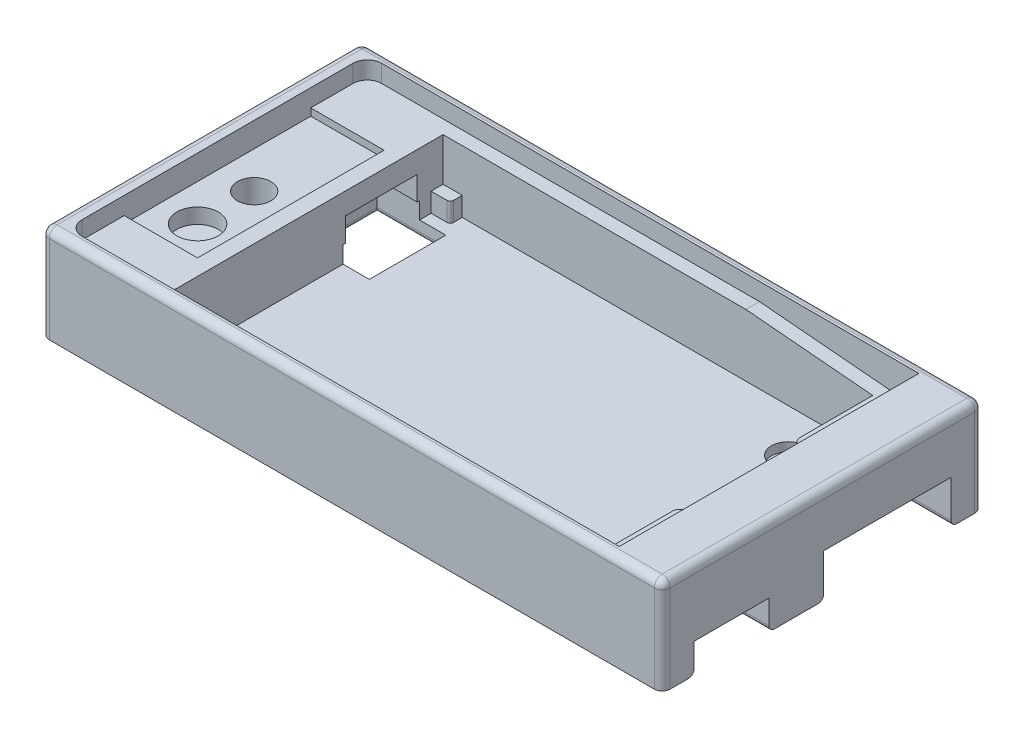
SolidWorks part; units mm, degrees
ref_plane "前视基准面" through (0, 0, 0) normal (0, 0, 1) x (1, 0, 0)
ref_plane "上视基准面" through (0, 0, 0) normal (0, 1, 0) x (1, 0, 0)
ref_plane "右视基准面" through (0, 0, 0) normal (1, 0, 0) x (0, 0, -1)
other "Configuration Table"
sketch "草图1" plane through (0, 0, 0) normal (0, 1, 0) x (1, 0, 0)
  line L0 (-38.945, 0) -> (38.945, 0) construction
  line L1 (-38.945, 20.1) -> (38.945, 20.1)
  line L2 (-38.945, 20.1) -> (-38.945, -20.1)
  line L3 (-38.945, -20.1) -> (38.945, -20.1)
  line L4 (38.945, 20.1) -> (38.945, -20.1)
  line L5 (-38.945, 20.1) -> (38.945, -20.1) construction
  line L6 (-38.945, -20.1) -> (38.945, 20.1) construction
  line L7 (-25.745, -17.1) -> (28.155, -17.1)
  line L8 (-25.745, -17.1) -> (-25.745, 17.1)
  line L9 (-25.745, 17.1) -> (28.155, 17.1)
  line L10 (28.155, -17.1) -> (28.155, 17.1)
  line L12 (32.245, 6.9973) -> (34.445, 6.9973)
  line L13 (32.245, 6.9973) -> (32.245, -6.9973)
  line L14 (32.245, -6.9973) -> (34.445, -6.9973)
  line L15 (34.445, 6.9973) -> (34.445, -6.9973)
  line L16 (-36.945, 18.8) -> (32.245, 18.8)
  line L17 (-36.945, 18.8) -> (-36.945, -18.8)
  line L18 (-36.945, -18.8) -> (32.245, -18.8)
  line L19 (32.245, 18.8) -> (32.245, -18.8)
  circle A0 centre (-32.345, 7.1) radius 2.6
  circle A1 centre (-32.345, 0) radius 2.1
  circle A2 centre (22.955, 11.6973) radius 2.1
  circle A3 centre (22.955, -11.6973) radius 2.1
  circle A4 centre (-32.345, -7.1) radius 2.6
  point P0 (0, 0)
  dimension "D1" = 4.2
  dimension "D6" = 5.2
  dimension "D2" = 5.2
  dimension "D3" = 5.4027
  dimension "D4" = 6.6
  dimension "D5" = 13
  dimension "D7" = 3
  dimension "D8" = 3
  dimension "D9" = 6.6
  dimension "D10" = 10.79
  dimension "D11" = 53.9
  dimension "D12" = 34.2
  dimension "D13" = 2.2
  dimension "D14" = 4.7
  dimension "D15" = 1.3
  dimension "D16" = 1.3
  dimension "D17" = 2
  dimension "D18" = 6.7
extrude "凸台-拉伸2" add sketch "草图1" along normal blind 2.2 contours L4 L1 L2 L3 L16 L19 L10 L12 L15 L14 L18 L17 | L15 L12 L10 L14 region at (0, 0, -19.2235) region at (33.345, 0, 0)
extrude "凸台-拉伸3" add sketch "草图1<4>" against normal blind 7.8 contours L19 L16 L17 L18 L7 L8 L9 A0 A1 A4 | L4 L1 L2 L3 L16 L19 L10 L12 L15 L14 L18 L17 | A4 | A0 | A1 | L15 L12 L13 L14 region at (0, 0, -19.2235) region at (33.345, 0, 0) region at (31.4575, 0, 0) region at (-32.345, 0, -7.1) region at (-32.345, 0, 0) region at (-32.345, 0, 7.1)
sketch "草图1<4>" plane through (0, 0, 0) normal (0, 1, 0) x (1, 0, 0) same geometry as "草图1"
sketch "草图2" plane through (0, 0, 0) normal (0, 1, 0) x (1, 0, 0)
  line L0 (-36.945, 18.8) -> (-36.945, -18.8) construction
  line L1 (-36.945, 11.7) -> (-27.745, 11.7)
  line L2 (-36.945, 11.7) -> (-36.945, -11.7)
  line L3 (-36.945, -11.7) -> (-27.745, -11.7)
  line L4 (-27.745, 11.7) -> (-27.745, -11.7)
  circle A0 centre (-32.345, 7.1) radius 2.6 construction
  circle A1 centre (-32.345, 7.1) radius 2.6 construction
  circle A2 centre (-32.345, -7.1) radius 2.6 construction
  circle A3 centre (-32.345, -7.1) radius 2.6 construction
  dimension "D1" = 4.6
  dimension "D2" = 4.6
  dimension "D3" = 4.6
extrude "切除-拉伸1" cut sketch "草图2" against normal blind 0.9
sketch "草图6" plane through (0, -0.9, 0) normal (0, 1, 0) x (1, 0, 0)
  circle A0 centre (-32.345, 7.1) radius 2.6 construction
  circle A1 centre (-32.345, 7.1) radius 2.6
  circle A2 centre (-32.345, -7.1) radius 2.6 construction
  circle A3 centre (-32.345, -7.1) radius 2.6
extrude "切除-拉伸2" cut sketch "草图6" against normal blind 1.9 contours A3 region at (-32.345, -0.9, 7.1)
sketch "草图7" plane through (0, -0.9, 0) normal (0, 1, 0) x (1, 0, 0)
  circle A0 centre (-32.345, 0) radius 2.1 construction
  circle A1 centre (-32.345, 0) radius 2.1
extrude "切除-拉伸3" cut sketch "草图7" against normal blind 1.1
sketch "草图8" plane through (0, -2, 0) normal (0, 1, 0) x (1, 0, 0)
  circle A0 centre (-32.345, 0) radius 1.2
  dimension "2.2" = 2.4
extrude "切除-拉伸4" cut sketch "草图8" against normal through all
sketch "草图9" plane through (0, -7.8, 0) normal (0, -1, 0) x (1, 0, 0)
  line L0 (38.945, -20.1) -> (38.945, 20.1) construction
  line L1 (-38.945, -20.1) -> (38.945, -20.1) construction
  line L2 (-38.945, -20.1) -> (-38.945, 20.1) construction
  line L3 (-38.945, 20.1) -> (38.945, 20.1) construction
  line L4 (38.945, -20.1) -> (38.945, 20.1)
  line L5 (-38.945, -20.1) -> (38.945, -20.1)
  line L6 (-38.945, -20.1) -> (-38.945, 20.1)
  line L7 (-38.945, 20.1) -> (38.945, 20.1)
extrude "凸台-拉伸4" add sketch "草图9" along normal blind 2
sketch "草图10" plane through (0, -7.8, 0) normal (0, 1, 0) x (1, 0, 0)
  circle A0 centre (22.955, -11.6973) radius 2.1 construction
  circle A1 centre (22.955, 11.6973) radius 2.1 construction
  circle A2 centre (22.955, -11.6973) radius 2.1
  circle A3 centre (22.955, 11.6973) radius 2.1
extrude "切除-拉伸5" cut sketch "草图10" against normal blind 1.1
sketch "草图11" plane through (0, -8.9, 0) normal (0, 1, 0) x (1, 0, 0)
  circle A0 centre (22.955, 11.6973) radius 1.2
  circle A1 centre (22.955, -11.6973) radius 1.2
  dimension "D1" = 2.4
  dimension "D2" = 2.4
extrude "切除-拉伸6" cut sketch "草图11" against normal through all
sketch "草图12" plane through (0, -9.8, 0) normal (0, -1, 0) x (1, 0, 0)
  line L0 (-25.745, -17.1) -> (28.155, -17.1) construction
  line L1 (-25.745, -17.1) -> (28.155, -17.1) construction
  line L7 (-30.5189, -4.85) -> (-26.0689, -4.85)
  line L8 (-30.5189, -4.85) -> (-30.5189, -13.85)
  line L9 (-30.5189, -13.85) -> (-26.0689, -13.85)
  line L10 (-26.0689, -4.85) -> (-26.0689, -13.85)
  line L11 (-30.5189, -4.85) -> (-26.0689, -13.85) construction
  line L12 (-30.5189, -13.85) -> (-26.0689, -4.85) construction
  line L13 (-28.2939, -9.35) -> (-23.0895, -9.35) construction
  line L14 (-31.0689, -4.55) -> (-26.0689, -4.55)
  line L15 (-31.0689, -4.55) -> (-31.0689, -14.15)
  line L16 (-31.0689, -14.15) -> (-26.0689, -14.15)
  line L17 (-26.0689, -4.55) -> (-26.0689, -14.15)
  point P6 (-28.2939, -9.35)
  dimension "D1" = 7.75
  dimension "D2" = 4.45
  dimension "D3" = 9
  dimension "D4" = 9.6
  dimension "D5" = 5
extrude "切除-拉伸7" cut sketch "草图12" against normal blind 7.1 contours L10 L7 L8 L9 region at (-28.2939, -9.8, -9.35)
extrude "切除-拉伸8" cut sketch "草图12<3>" against normal offset from surface (4.1 mm away) 3 contours L17 L14 L15 L16 L9 L8 L7 region at (-30.6271, -9.8, -9.35) up to face at (-28.2939, -2.7, -9.35)
sketch "草图12<3>" plane through (0, -9.8, 0) normal (0, -1, 0) x (1, 0, 0) same geometry as "草图12"
sketch "草图13" plane through (-26.0689, 0, 0) normal (-1, 0, 0) x (0, 0, 1)
  line L4 (-4.85, -2.7) -> (-13.85, -2.7)
  line L5 (-4.85, -2.7) -> (-13.85, -2.7)
  line L9 (-13.85, -2.7) -> (-13.85, -5.7)
  line L11 (-13.85, -5.7) -> (-14.15, -5.7)
  line L12 (-14.15, -9.8) -> (-4.55, -9.8)
  line L13 (-13.85, -5.7) -> (-14.15, -5.7)
  line L14 (-14.15, -5.7) -> (-14.15, -9.8)
  line L15 (-4.85, -5.7) -> (-4.85, -2.7)
  line L17 (-13.85, -2.7) -> (-13.85, -5.7)
  line L20 (-14.15, -9.8) -> (-4.55, -9.8)
  line L23 (-4.85, -5.7) -> (-4.85, -2.7)
  line L24 (-14.15, -5.7) -> (-14.15, -9.8)
  line L25 (-4.55, -9.8) -> (-4.55, -5.7)
  line L26 (-4.55, -9.8) -> (-4.55, -5.7)
  line L27 (-4.55, -5.7) -> (-4.85, -5.7)
  line L28 (-4.55, -5.7) -> (-4.85, -5.7)
  dimension "D1" = 0
extrude "切除-拉伸9" cut sketch "草图13" against normal up to surface (0.3239 mm away) up to face at (-25.745, -3.9, 0)
sketch "草图14" plane through (-25.745, 0, 0) normal (-1, 0, 0) x (0, 0, 1)
  line L4 (-14.15, -7.8) -> (-14.15, -9.8)
  line L5 (-14.15, -9.8) -> (-4.55, -9.8)
  line L7 (-4.55, -7.8) -> (-14.15, -7.8)
  line L9 (-14.15, -9.8) -> (-4.55, -9.8)
  line L11 (-4.55, -7.8) -> (-14.15, -7.8)
  line L12 (-14.15, -7.8) -> (-14.15, -9.8)
  line L14 (-4.55, -9.8) -> (-4.55, -7.8)
  line L15 (-4.55, -9.8) -> (-4.55, -7.8)
  dimension "D1" = 0
extrude "切除-拉伸10" cut sketch "草图14" against normal blind 3.3
fillet "圆角1" radius 1.8 4 edges at (32.245, 1.1, 18.8) (32.245, 1.1, -18.8) (-36.945, 1.1, -18.8) (-36.945, 1.1, 18.8)
fillet "圆角2" radius 1 8 edges at (38.945, -3.8, -20.1) (38.945, 2.2, 0) (38.945, -3.8, 20.1) (0, 2.2, -20.1) (-38.945, -3.8, -20.1) (0, 2.2, 20.1) (-38.945, 2.2, 0) (-38.945, -3.8, 20.1)
sketch "草图15" plane through (0, -7.8, 0) normal (0, 1, 0) x (1, 0, 0)
  line L0 (0, 0) -> (25.0264, 0) construction
  line L1 (-25.745, 17.1) -> (-23.345, 17.1)
  line L2 (-25.745, 17.1) -> (-25.745, 15.6)
  line L3 (-25.745, 15.6) -> (-23.345, 15.6)
  line L4 (-23.345, 17.1) -> (-23.345, 15.6)
  line L5 (-25.745, -15.6) -> (-23.345, -15.6)
  line L6 (-23.345, -17.1) -> (-23.345, -15.6)
  line L7 (-25.745, -17.1) -> (-23.345, -17.1)
  line L8 (-25.745, -17.1) -> (-25.745, -15.6)
  dimension "D1" = 2.4
  dimension "D2" = 1.5
extrude "凸台-拉伸5" add sketch "草图15" along normal blind 2.4
sketch "草图16" plane through (0, 0, 0) normal (0, 1, 0) x (1, 0, 0)
  line L0 (0, 0) -> (31.9375, 0) construction
  line L1 (28.155, -17.1) -> (28.155, 17.1) construction
  line L3 (30.2966, 8) -> (30.2966, -8)
  line L4 (32.245, 17) -> (32.245, -17) construction
  line L6 (30.2966, 10.6491) -> (30.2966, 8)
  line L7 (30.2966, -10.6491) -> (30.2966, -8)
  arc A0 (29.9791, 7.2593) -> (30.2966, 10.6491) centre (31.5254, 8.8242) cw
  arc A1 (29.9791, -7.2593) -> (30.2966, -10.6491) centre (31.5254, -8.8242) ccw
  ellipse E0 centre (28.155, 0) end of major axis (28.155, -8.1106) minor radius 4.09 (29.9791, -7.2593) -> (29.9791, 7.2593) ccw
  dimension "D1" = 2.2
revolve "切除-旋转1" [suppressed] cut sketch "草图16" angle 360 about L3
sketch "草图17" plane through (0, -7.8, 0) normal (0, 1, 0) x (1, 0, 0)
  circle A1 centre (-32.345, 0) radius 1.2
  circle A2 centre (-32.345, 0) radius 1.2
  dimension "D1" = 0
extrude "切除-拉伸11" cut sketch "草图17" against normal through all
sketch "草图19" plane through (0, 0, 20.1) normal (0, 0, 1) x (1, 0, 0)
  line L0 (12.245, 0) -> (34.1356, 0.2) construction
  line L1 (32.245, 2.2) -> (30.445, 2.2) construction
  line L2 (12.245, 0) -> (32.245, 2) construction
  line L6 (12.245, 0) -> (12.245, 2)
  line L11 (12.245, 0) -> (34.045, -2) construction
  line L12 (12.245, 0) -> (32.2683, -1.7518)
  line L13 (12.245, 0) -> (33.7165, -4.2678) construction
  line L14 (32.245, 2) -> (32.245, 0) construction
  line L15 (32.245, 0) -> (30.245, 0) construction
  line L17 (12.245, 2) -> (12.245, 3)
  line L18 (12.245, 3) -> (32.245, 3)
  line L19 (32.245, 2) -> (32.245, 3)
  line L20 (32.245, 2.2) -> (30.445, 2.2) construction
  line L21 (-35.145, 0) -> (30.445, 0) construction
  line L22 (-35.145, 0) -> (30.245, 0) construction
  line L23 (12.245, 2) -> (32.245, 2) construction
  line L24 (34.1416, 0) -> (32.3448, 0) construction
  line L25 (30.245, 0) -> (34.045, 0) construction
  line L26 (30.245, 0) -> (30.245, -2) construction
  line L27 (30.245, -2) -> (34.045, -2) construction
  line L28 (34.045, 0) -> (34.045, -2) construction
  line L29 (33.7165, -4.2678) -> (25.7165, -2.6777)
  line L30 (25.7165, -2.6777) -> (25.8467, -1.19)
  line L31 (34.1356, 0.2) -> (32.3439, 0.1836)
  circle A0 centre (12.245, 0) radius 20.0998 construction
  arc A3 (32.245, 2) -> (32.2683, -1.7518) centre (12.245, 0) cw
  circle A4 centre (12.245, 0) radius 21.8916 construction
  arc A5 (33.7165, -4.2678) -> (34.1356, 0.2) centre (12.245, 0) ccw
  line M8 (37.945, 1.2) -> (-37.945, 1.2)
  dimension "D1" = 2
  dimension "D2" = 20
  dimension "D3" = 5
  dimension "D4" = 2
  dimension "D5" = 20
  dimension "D6" = 6
  dimension "D7" = 1
  dimension "D8" = 1.8
  dimension "D9" = 2
  dimension "D10" = 8
  dimension "D11" = 0.2
extrude "切除-拉伸12" cut sketch "草图19" against normal up to surface (38.9 mm away) from surface contours L6 L12 M8 | L6 M8 region at (23.6992, 0.0997, 20.1) region at (22.2527, 2.0995, 20.1) up to face at (-2.35, 1.1, -18.8) starting at face at (-2.35, 1.1, 18.8)
extrude "切除-拉伸13" cut sketch "草图19<3>" against normal up to vertex (27.0973 mm away) from vertex contours L27 L12 L13 region at (30.7271, -2.2329, 20.1) up to point (34.445, 0, -6.9973) starting at point (34.445, 0, 6.9973)
sketch "草图19<3>" plane through (0, 0, 20.1) normal (0, 0, 1) x (1, 0, 0) same geometry as "草图19"
sketch "草图20" plane through (0.3554, 2.3632, 0) normal (0.195, 0.9808, 0) x (0.9808, -0.195, 0)
  line L0 (0.1121, 0) -> (28.3434, 0) construction
  line L1 (28.3434, 6.9973) -> (28.3434, -6.9973) construction
  line L2 (28.3434, 6.9973) -> (28.3434, -6.9973) construction
  line L3 (28.3434, 5.3609) -> (28.3434, -5.3609)
  line L4 (28.3434, 0) -> (31.3095, 0) construction
  line L5 (31.3095, 18.8) -> (31.3095, -18.8) construction
  line L6 (29.3869, 4.2263) -> (28.3434, 5.3609) construction
  line L9 (28.3434, -5.3609) -> (28.3434, 5.3609) construction
  ellipse E0 centre (28.3434, 0) end of major axis (28.3434, 5.3609) minor radius 2.9661 (28.3434, 5.3609) -> (28.3434, -5.3609) cw
revolve "切除-旋转2" [suppressed] cut sketch "草图20" angle 360 about L3
fillet "圆角4" [suppressed] radius 1
fillet "圆角5" radius 0.4 2 edges at (-23.345, -6.6, 15.6) (-23.345, -6.6, -15.6)
sketch "草图21" plane through (0, -2, 0) normal (0, 1, 0) x (1, 0, 0)
  circle A1 centre (-32.345, 0) radius 2.1
  circle A2 centre (-32.345, 0) radius 2.1
  dimension "D1" = 0
extrude "切除-拉伸14" cut sketch "草图21" against normal up to surface (6.9 mm away) up to face at (22.955, -8.9, -10.4973)
sketch "草图22" plane through (0, -9.8, 0) normal (0, -1, 0) x (1, 0, 0)
  line L0 (0, 0) -> (39.25, 0) construction
  line L2 (-38.945, 14.6675) -> (-38.945, 5.2675)
  line L3 (31.045, 16.1208) -> (38.945, 16.1208)
  line L4 (31.045, 16.1208) -> (31.045, 6.7208)
  line L5 (31.045, 6.7208) -> (38.945, 6.7208)
  line L6 (38.945, 16.1208) -> (38.945, 6.7208)
  line L7 (31.045, 16.1208) -> (38.945, 6.7208) construction
  line L8 (31.045, 6.7208) -> (38.945, 16.1208) construction
  line L9 (-38.945, 14.6675) -> (-31.045, 14.6675)
  line L10 (-38.945, 5.2675) -> (-31.045, 5.2675)
  line L11 (-31.045, 14.6675) -> (-31.045, 5.2675)
  line L13 (38.945, -19.1) -> (38.945, 19.1) construction
  line L14 (-38.945, 19.1) -> (-38.945, -19.1) construction
  point P5 (34.995, 11.4208)
  dimension "D1" = 7.9
  dimension "D2" = 9.4
extrude "切除-拉伸15" cut sketch "草图22" against normal blind 3.7
sketch "草图23" plane through (0, -9.8, 0) normal (0, -1, 0) x (1, 0, 0)
  line L1 (38.945, -16.1357) -> (30.545, -16.1357)
  line L2 (38.945, -16.1357) -> (38.945, -0.1357)
  line L3 (38.945, -0.1357) -> (30.545, -0.1357)
  line L4 (30.545, -16.1357) -> (30.545, -0.1357)
  line L6 (32.2683, -18.8) -> (12.245, -18.8) construction
  line L7 (32.2683, -18.8) -> (12.245, -18.8) construction
  line L8 (38.945, -19.1) -> (38.945, 6.7208) construction
  line L9 (38.945, -19.1) -> (38.945, 6.7208) construction
  dimension "D1" = 8.4
  dimension "D2" = 16
extrude "切除-拉伸16" cut sketch "草图23" against normal blind 5.4
fillet "圆角6" radius 0.7 13 edges at (-34.995, -9.8, 5.2675) (34.745, -9.8, -16.1357) (30.545, -9.8, -8.1357) (34.745, -9.8, -0.1357) (34.995, -9.8, 6.7208) (34.995, -9.8, 16.1208) (31.045, -9.8, 11.4208) (-22.445, -9.8, -9.35) (-26.7569, -9.8, -14.15) (-31.0689, -9.8, -9.35) (-26.7569, -9.8, -4.55) (-31.045, -9.8, 9.9675) (-34.995, -9.8, 14.6675)
fillet "圆角7" radius 1 3 edges at (28.155, -2.2771, 6.9973) (28.155, -2.2771, -6.9973) (28.155, -3.1623, 0)
